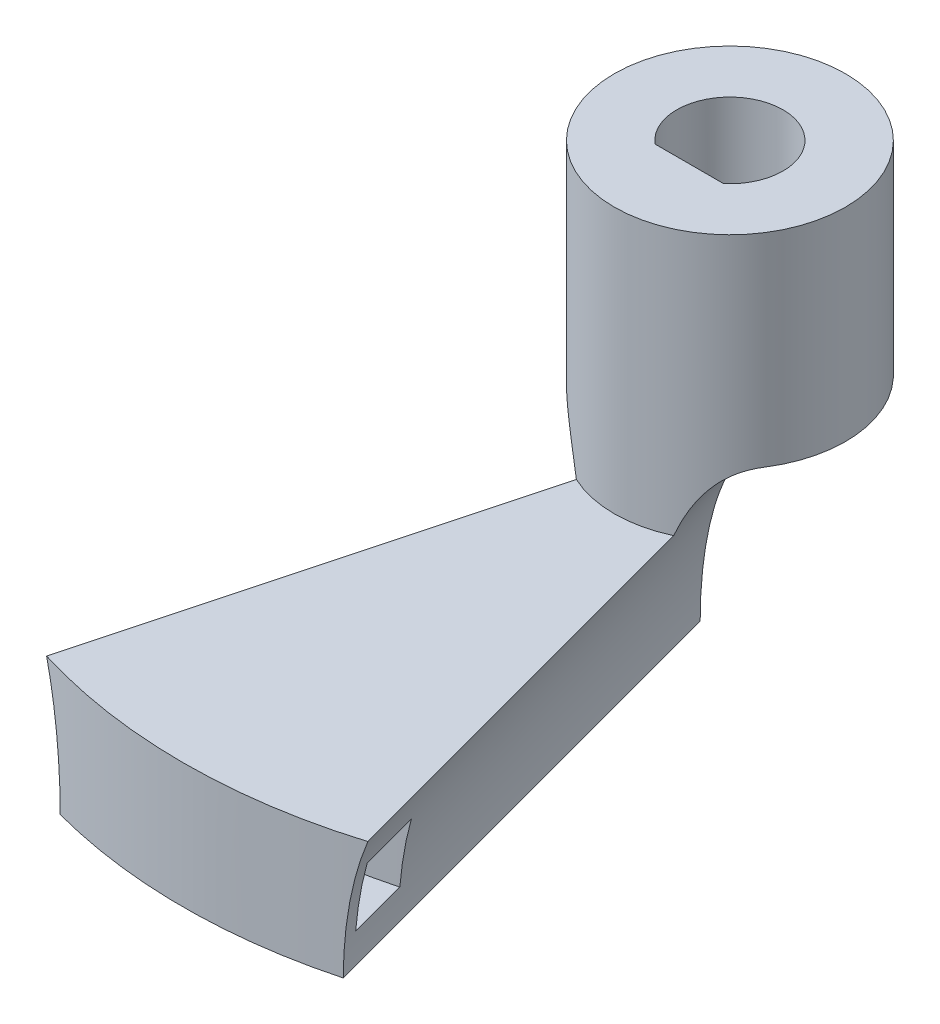
SolidWorks part; units mm, degrees
ref_plane "Front Plane" through (0, 0, 0) normal (0, 0, 1) x (1, 0, 0)
ref_plane "Top Plane" through (0, 0, 0) normal (0, 1, 0) x (1, 0, 0)
ref_plane "Right Plane" through (0, 0, 0) normal (1, 0, 0) x (0, 0, -1)
sketch "Sketch1" plane through (0, 0, 0) normal (0, 1, 0) x (1, 0, 0)
  line L0 (-1.0954, -1.3) -> (1.0954, -1.3)
  line L1 (0, -1.3) -> (0, -1.7)
  circle A0 centre (0, 0) radius 1.7
  circle A1 centre (0, 0) radius 17.5
  dimension "D1" = 3.4
  dimension "D2" = 35
  dimension "D3" = 0.4
extrude "Boss-Extrude1" add sketch "Sketch1" along normal blind 4 contours A1 A0 | L1 A0 L0 | L0 A0 L1
sketch "Sketch2" plane through (0, 4, 0) normal (0, 1, 0) x (1, 0, 0)
  line L1 (1.7, 0) -> (3.7, 0) construction
  line L2 (-1.0954, -1.3) -> (1.0954, -1.3)
  circle A0 centre (0, 0) radius 3.7
  arc A1 (1.0954, -1.3) -> (-1.0954, -1.3) centre (0, 0) ccw construction
  arc A2 (-1.0954, -1.3) -> (1.0954, -1.3) centre (0, 0) cw
  dimension "D2" = 1.7
  dimension "D1" = 2
extrude "Boss-Extrude2" add sketch "Sketch2" along normal blind 8.5
sketch "Sketch3" plane through (0, 12.5, 0) normal (0, 1, 0) x (1, 0, 0)
  line L0 (0, 0) -> (0, -3.7) construction
  circle A0 centre (0, 0) radius 3.7 construction
sketch "Sketch4" plane through (0, 0, 0) normal (0, -1, 0) x (1, 0, 0)
  line L0 (0, 0) -> (0, 17.5) construction
  circle A0 centre (0, 0) radius 17.5 construction
ref_plane "Plane1" through (0, 0, 0) normal (1, 0, 0) x (0, 0, -1)
ref_plane "Plane2" through (12.5, 0, 0) normal (1, 0, 0) x (0, 0, -1)
sketch "Sketch5" plane through (12.5, 0, 0) normal (1, 0, 0) x (0, 0, -1)
  line L0 (0, 0) -> (0, 4) construction
  line L4 (17.5, 4) -> (-17.5, 4) construction
  circle A0 centre (0, 2) radius 0.75
  dimension "D1" = 1.5
sketch3d "3DSketch1"
  line L0 (12.5, 0, 0) -> (12.5, 4, 0) construction
  line L1 (12.5, 2, 0) -> (9.1368, 2, 0)
  line L3 (9.1368, 2, 0) -> (7.1368, 2, 0) construction
  line L4 (7.1368, 0, 0) -> (7.1368, -2.2816, 0)
  arc A0 (7.1368, 0, 0) -> (9.1368, 2, 0) centre (9.1368, 0, 0) ccw
  point P6 (7.1368, 2, 0)
  point P8 (9.1368, 0, -2)
  dimension "D1" = 2
ref_plane "Plane3" through (0, 2, 0) normal (0, 1, 0) x (1, 0, 0)
sketch "Sketch21" plane through (0, 2, 0) normal (0, 1, 0) x (1, 0, 0)
  circle A0 centre (0, 0) radius 17
  circle A1 centre (0, 0) radius 15
  dimension "D1" = 34
  dimension "D2" = 2
extrude "Cut-Extrude1" cut sketch "Sketch21" against normal mid plane 2
sketch "Sketch24" plane through (0, 0, 0) normal (0, -1, 0) x (1, 0, 0)
  line L0 (0, 0) -> (-8.7351, 32.6)
  line L1 (0, 0) -> (0, 17.5) construction
  line L2 (0, 33.75) -> (0, 0) construction
  line L3 (0, 0) -> (8.7351, 32.6)
  circle A0 centre (0, 0) radius 17.5 construction
  arc A1 (-8.7351, 32.6) -> (8.7351, 32.6) centre (0, 0) ccw
  spline S0 degree 3 poles (-8.7351, 32.6) (-8.3901, 32.6924) (-7.8638, 32.8245) (-7.1316, 32.9897) (-6.5276, 33.1148) (-5.8984, 33.2327) (-5.2675, 33.3384) (-4.6146, 33.4353) (-3.9291, 33.5231) (-3.168, 33.604) (-2.4108, 33.6668) (-1.341, 33.7306) (-0.5515, 33.75) (0, 33.75) knots 0 0 0 0 0.121279 0.184207 0.254866 0.330701 0.401525 0.472062 0.554811 0.636143 0.731935 0.812746 1 1 1 1
  spline S1 degree 3 poles (8.7351, 32.6) (8.3901, 32.6924) (7.8638, 32.8245) (7.1316, 32.9897) (6.5276, 33.1148) (5.8984, 33.2327) (5.2675, 33.3384) (4.6146, 33.4353) (3.9291, 33.5231) (3.168, 33.604) (2.4108, 33.6668) (1.341, 33.7306) (0.5515, 33.75) (0, 33.75) knots 0 0 0 0 0.121279 0.184207 0.254866 0.330701 0.401525 0.472062 0.554811 0.636143 0.731935 0.812746 1 1 1 1
  dimension "D1" = 15
extrude "Cut-Extrude2" cut sketch "Sketch24" against normal blind 6
fillet "Fillet1" radius 6 1 edges at (-0.653, 6, 2.437) second distance 2.5 first distance on face at (-1.9451, 3.3333, 7.2592)
fillet "Fillet2" radius 6 1 edges at (0.653, 6, 2.437) second distance 2.5 first distance on face at (1.9451, 3.3333, 7.2592)
fillet "Fillet4" radius 1.75 2 edges
